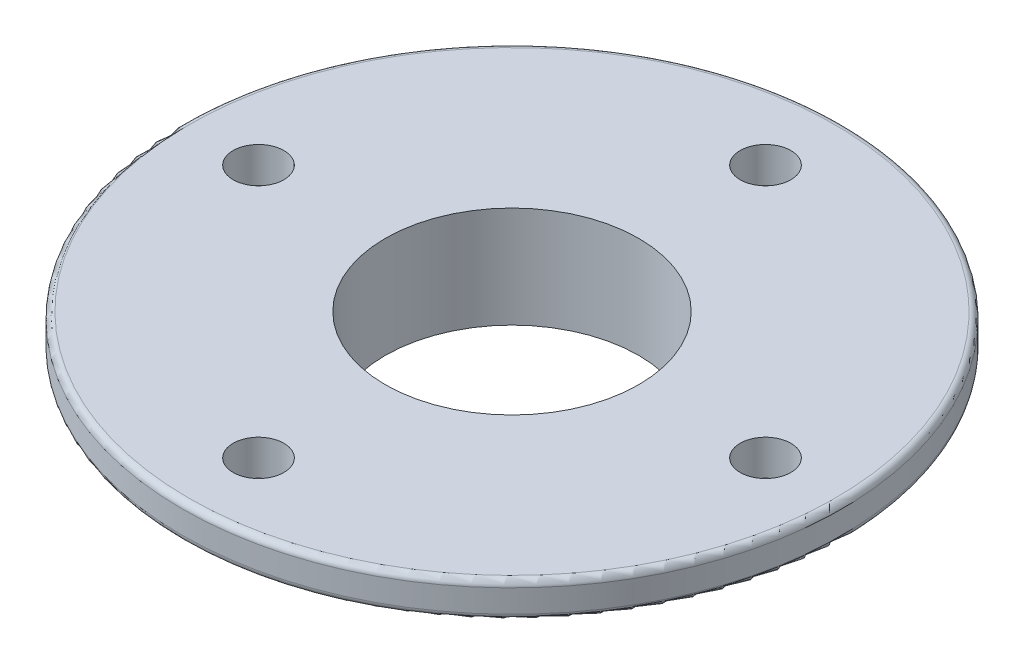
SolidWorks part; units mm, degrees
ref_plane "Front" through (0, 0, 0) normal (0, 0, 1) x (1, 0, 0)
ref_plane "Top" through (0, 0, 0) normal (0, 1, 0) x (1, 0, 0)
ref_plane "Right" through (0, 0, 0) normal (1, 0, 0) x (0, 0, -1)
sketch "Sketch1" plane through (0, 0, 0) normal (0, 1, 0) x (1, 0, 0)
  circle A0 centre (0, 0) radius 5
  circle A1 centre (0, 0) radius 7
  dimension "D1" = 10
  dimension "D2" = 14
extrude "Boss-Extrude1" add sketch "Sketch1" along normal blind 2.6
ref_plane "Plane1" through (0, 2.6, 0) normal (0, 1, 0) x (1, 0, 0)
sketch "Sketch2" plane through (0, 2.6, 0) normal (0, 1, 0) x (1, 0, 0)
  circle A0 centre (0, 0) radius 13
  circle A1 centre (0, 0) radius 5
  circle A2 centre (0, 0) radius 5 construction
  dimension "D2" = 26
extrude "Boss-Extrude2" add sketch "Sketch2" along normal blind 1.4
sketch "Sketch3" plane through (0, 4, 0) normal (0, 1, 0) x (1, 0, 0)
  line L0 (0, 0) -> (0, 13) construction
  circle A0 centre (0, 0) radius 13 construction
  circle A1 centre (0, 10) radius 1
  dimension "D1" = 2
  dimension "D2" = 10
extrude "Cut-Extrude1" cut sketch "Sketch3" against normal through all
pattern_circular "CirPattern1" count 4 over 360 about axis through (0, 2.6, 0) along (0, -1, 0) of "Cut-Extrude1"
fillet "Fillet1" radius 0.25 2 edges at (0, 4, 13) (0, 2.6, 13)
